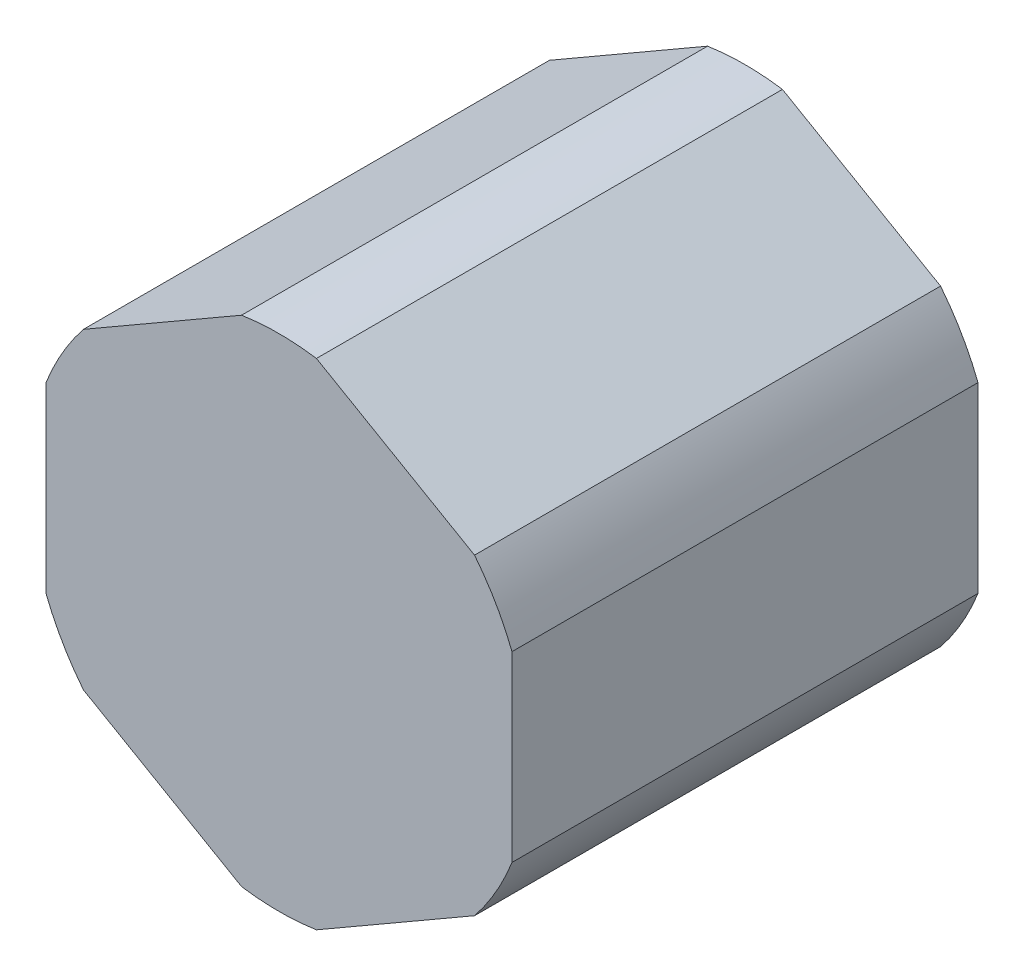
SolidWorks part; units mm, degrees
material "7075-T6 (SN)"
ref_plane "Front Plane" through (0, 0, 0) normal (0, 0, 1) x (1, 0, 0)
ref_plane "Top Plane" through (0, 0, 0) normal (0, 1, 0) x (1, 0, 0)
ref_plane "Right Plane" through (0, 0, 0) normal (1, 0, 0) x (0, 0, -1)
sketch "Sketch1" plane through (0, 0, 0) normal (0, 0, 1) x (1, 0, 0)
  line L1 (6.35, 3.6662) -> (0, 7.3323)
  line L2 (0, 7.3323) -> (-6.35, 3.6662)
  line L3 (-6.35, 3.6662) -> (-6.35, -3.6662)
  line L4 (-6.35, -3.6662) -> (0, -7.3323)
  line L5 (0, -7.3323) -> (6.35, -3.6662)
  line L6 (6.35, -3.6662) -> (6.35, 3.6662)
  circle A0 centre (0, 0) radius 6.35 construction
  circle A1 centre (0, 0) radius 6.8199
  dimension "D1" = 12.7
  dimension "D2" = 13.6398
extrude "Boss-Extrude1" add sketch "Sketch1" along normal blind 12.7 contours L6 A1 L1 L2 L3 L4 L5 region at (0, 0, 0)
